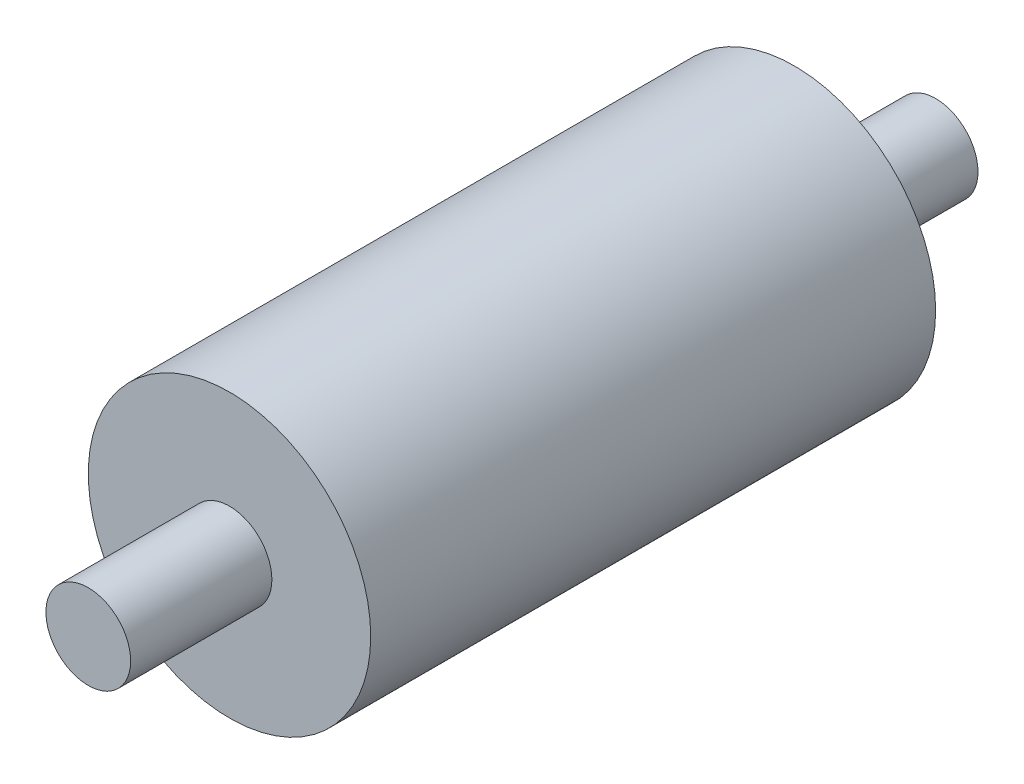
SolidWorks part; units mm, degrees
ref_plane "Front Plane" through (0, 0, 0) normal (0, 0, 1) x (1, 0, 0)
ref_plane "Top Plane" through (0, 0, 0) normal (0, 1, 0) x (1, 0, 0)
ref_plane "Right Plane" through (0, 0, 0) normal (1, 0, 0) x (0, 0, -1)
sketch "Sketch1" plane through (0, 0, 0) normal (0, 0, 1) x (1, 0, 0)
  circle A0 centre (0, 0) radius 10
  dimension "D1" = 20
extrude "Boss-Extrude1" add sketch "Sketch1" along normal blind 20 and the other way blind 20
sketch "Sketch2" plane through (0, 0, 20) normal (0, 0, 1) x (1, 0, 0)
  circle A0 centre (0, 0) radius 3
  dimension "D1" = 6
extrude "Boss-Extrude2" add sketch "Sketch2" along normal blind 10
mirror "Mirror1" about plane through (0, 0, 0) normal (0, 0, 1) of "Boss-Extrude2"
